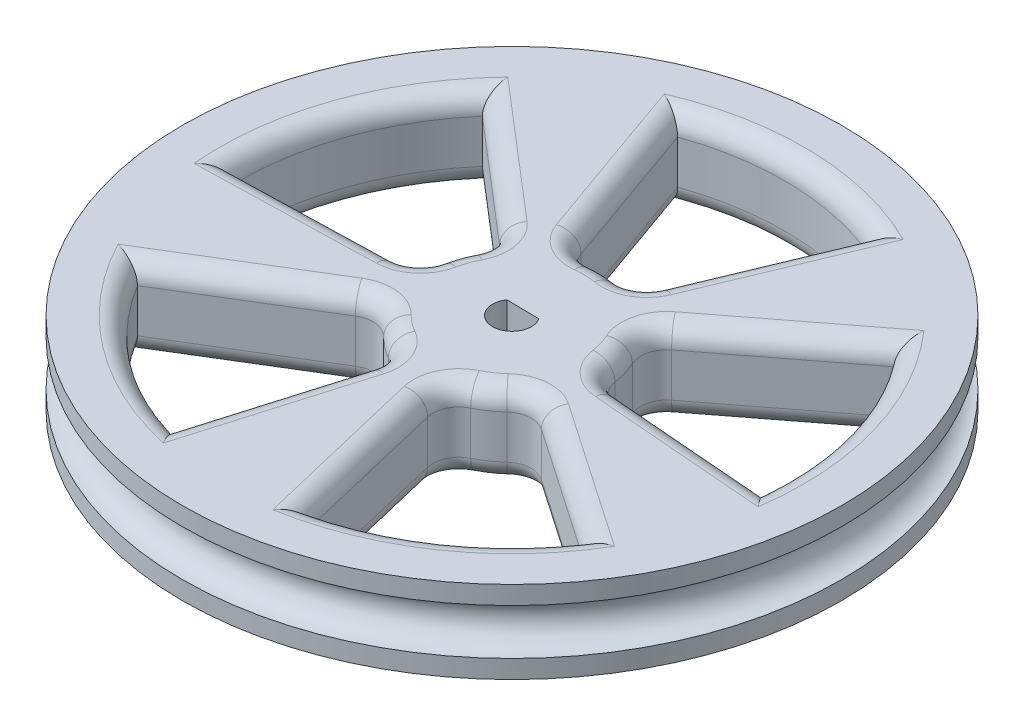
SolidWorks part; units mm, degrees
ref_plane "정면" through (0, 0, 0) normal (0, 0, 1) x (1, 0, 0)
ref_plane "윗면" through (0, 0, 0) normal (0, 1, 0) x (1, 0, 0)
ref_plane "우측면" through (0, 0, 0) normal (1, 0, 0) x (0, 0, -1)
sketch "Sketch1" plane through (0, 0, 0) normal (0, 1, 0) x (1, 0, 0)
  line L0 (-1.2392, 0.8452) -> (1.2634, 0.8085)
  line L1 (6.9576, 5.3472) -> (16.6506, 12.7967)
  line L2 (8.7469, -0.7016) -> (20.9328, -1.679)
  line L3 (-2.9355, 8.2694) -> (-7.0251, 19.7901)
  line L4 (3.3702, 8.102) -> (8.0654, 19.3894)
  line L5 (7.2355, -4.9647) -> (17.3157, -11.8813)
  line L6 (2.0357, -8.5356) -> (4.8718, -20.4271)
  line L7 (-2.4858, -8.4155) -> (-5.9489, -20.1398)
  line L8 (-7.4887, -4.5737) -> (-17.9218, -10.9457)
  line L9 (-8.7718, -0.2364) -> (-20.9924, -0.5658)
  line L10 (-6.664, 5.7089) -> (-15.9481, 13.6623)
  circle A0 centre (0, 0) radius 25.4
  arc A1 (-1.2392, 0.8452) -> (1.2634, 0.8085) centre (0, 0) ccw
  arc A2 (1.185, 6.899) -> (-0.8172, 6.9521) centre (0, 0) ccw
  arc A3 (8.0654, 19.3894) -> (-7.0251, 19.7901) centre (0, 0) ccw
  arc A4 (1.185, 6.899) -> (3.3702, 8.102) centre (1.5235, 8.8701) ccw
  arc A5 (-0.8172, 6.9521) -> (-2.9355, 8.2694) centre (-1.0507, 8.9385) cw
  arc A6 (6.9275, 1.0049) -> (6.3593, 2.9255) centre (0, 0) ccw
  arc A7 (20.9328, -1.679) -> (16.6506, 12.7967) centre (0, 0) ccw
  arc A8 (6.9275, 1.0049) -> (8.7469, -0.7016) centre (8.9068, 1.292) ccw
  arc A9 (6.3593, 2.9255) -> (6.9576, 5.3472) centre (8.1763, 3.7614) cw
  arc A10 (3.0964, -6.2779) -> (4.7475, -5.1441) centre (0, 0) ccw
  arc A11 (4.8718, -20.4271) -> (17.3157, -11.8813) centre (0, 0) ccw
  arc A12 (3.0964, -6.2779) -> (2.0357, -8.5356) centre (3.9811, -8.0716) ccw
  arc A13 (4.7475, -5.1441) -> (7.2355, -4.9647) centre (6.1039, -6.6138) cw
  arc A14 (-5.0138, -4.8849) -> (-3.4252, -6.1047) centre (0, 0) ccw
  arc A15 (-17.9218, -10.9457) -> (-5.9489, -20.1398) centre (0, 0) ccw
  arc A16 (-5.0138, -4.8849) -> (-7.4887, -4.5737) centre (-6.4463, -6.2806) ccw
  arc A17 (-3.4252, -6.1047) -> (-2.4858, -8.4155) centre (-4.4039, -7.8489) cw
  arc A18 (-6.1951, 3.2589) -> (-6.8644, 1.3711) centre (0, 0) ccw
  arc A19 (-15.9481, 13.6623) -> (-20.9924, -0.5658) centre (0, 0) ccw
  arc A20 (-6.1951, 3.2589) -> (-6.664, 5.7089) centre (-7.9652, 4.19) ccw
  arc A21 (-6.8644, 1.3711) -> (-8.7718, -0.2364) centre (-8.8257, 1.7629) cw
  point P48 (0, 0)
  dimension "D1" = 5
extrude "Boss-Extrude1" add sketch "Sketch1" along normal blind 6.35
sketch "Sketch3" plane through (0, 0, 0) normal (-0.5658, 0, 0.8246) x (0.8246, 0, 0.5658)
  line L0 (0, 6.418) -> (0, 0) construction
  line L1 (-25.4, 6.35) -> (-25.4, 0) construction
  circle A0 centre (-25.4, 3.175) radius 1.7653
revolve "Cut-Revolve3" cut sketch "Sketch3" angle 360 about L0
fillet "Fillet1" radius 1.5 30 edges at (5.7178, 6.35, -13.7457) (2.4881, 6.35, -7.1181) (0.1858, 6.35, -6.9975) (-2.1069, 6.35, -7.2401) (-4.9803, 6.35, -14.0298) (0.5574, 6.35, -20.9926) (-19.7929, 6.35, -7.0172) (-14.8821, 6.35, 0.4011) (-7.5368, 6.35, -0.2336) (-6.5976, 6.35, -2.3391) (-6.0008, 6.35, -4.5659) (-11.3061, 6.35, -9.6856) (11.8882, 6.35, 17.311) (12.2756, 6.35, 8.423) (5.9601, 6.35, 4.619) (3.9627, 6.35, 5.7703) (2.171, 6.35, 7.2211) (3.4538, 6.35, 14.4813) (20.1374, 6.35, -5.957) (11.8041, 6.35, -9.0719) (6.2347, 6.35, -4.241) (6.7125, 6.35, -1.9857) (7.5385, 6.35, 0.1667) (14.8398, 6.35, 1.1903) (-12.7901, 6.35, 16.6557) (-4.2174, 6.35, 14.2776) (-2.5511, 6.35, 7.0957) (-4.2634, 6.35, 5.5519) (-6.1968, 6.35, 4.2962) (-12.7053, 6.35, 7.7597)
fillet "Fillet5" radius 1.5 30 edges at (-6.5976, 0, -2.3391) (-7.5368, 0, -0.2336) (-14.8821, 0, 0.4011) (-19.7929, 0, -7.0172) (-11.3061, 0, -9.6856) (-6.0008, 0, -4.5659) (3.9627, 0, 5.7703) (5.9601, 0, 4.619) (12.2756, 0, 8.423) (11.8882, 0, 17.311) (3.4538, 0, 14.4813) (2.171, 0, 7.2211) (0.1858, 0, -6.9975) (-2.1069, 0, -7.2401) (-4.9803, 0, -14.0298) (0.5574, 0, -20.9926) (5.7178, 0, -13.7457) (2.4881, 0, -7.1181) (6.7125, 0, -1.9857) (6.2347, 0, -4.241) (11.8041, 0, -9.0719) (20.1374, 0, -5.957) (14.8398, 0, 1.1903) (7.5385, 0, 0.1667) (-4.2634, 0, 5.5519) (-2.5511, 0, 7.0957) (-4.2174, 0, 14.2776) (-12.7053, 0, 7.7597) (-6.1968, 0, 4.2962) (-12.7901, 0, 16.6557)
